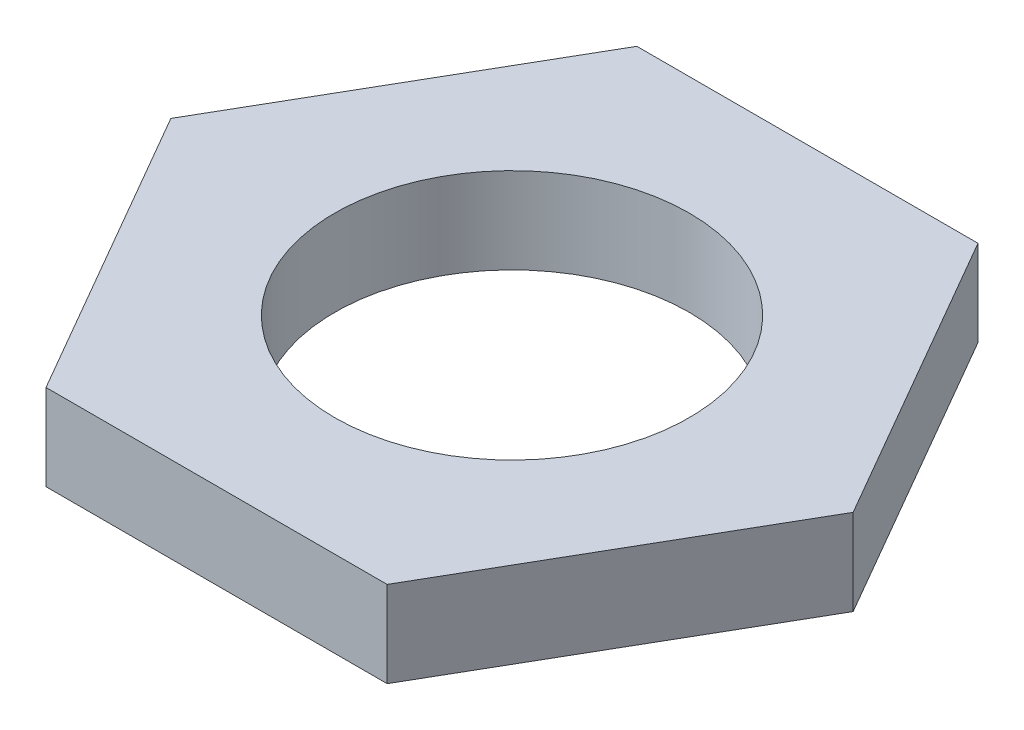
SolidWorks part; units mm, degrees
ref_plane "Front Plane" through (0, 0, 0) normal (0, 0, 1) x (1, 0, 0)
ref_plane "Top Plane" through (0, 0, 0) normal (0, 1, 0) x (1, 0, 0)
ref_plane "Right Plane" through (0, 0, 0) normal (1, 0, 0) x (0, 0, -1)
sketch "Sketch1" plane through (0, 0, 0) normal (0, 1, 0) x (1, 0, 0)
  line L1 (-4.5827, -7.9375) -> (4.5827, -7.9375)
  line L2 (4.5827, -7.9375) -> (9.1654, 0)
  line L3 (9.1654, 0) -> (4.5827, 7.9375)
  line L4 (4.5827, 7.9375) -> (-4.5827, 7.9375)
  line L5 (-4.5827, 7.9375) -> (-9.1654, 0)
  line L6 (-9.1654, 0) -> (-4.5827, -7.9375)
  circle A0 centre (0, 0) radius 7.9375 construction
  circle A1 centre (0, 0) radius 4.7625
  dimension "D2" = 9.525
  dimension "D1" = 15.875
extrude "Boss-Extrude1" add sketch "Sketch1" along normal blind 2.31
